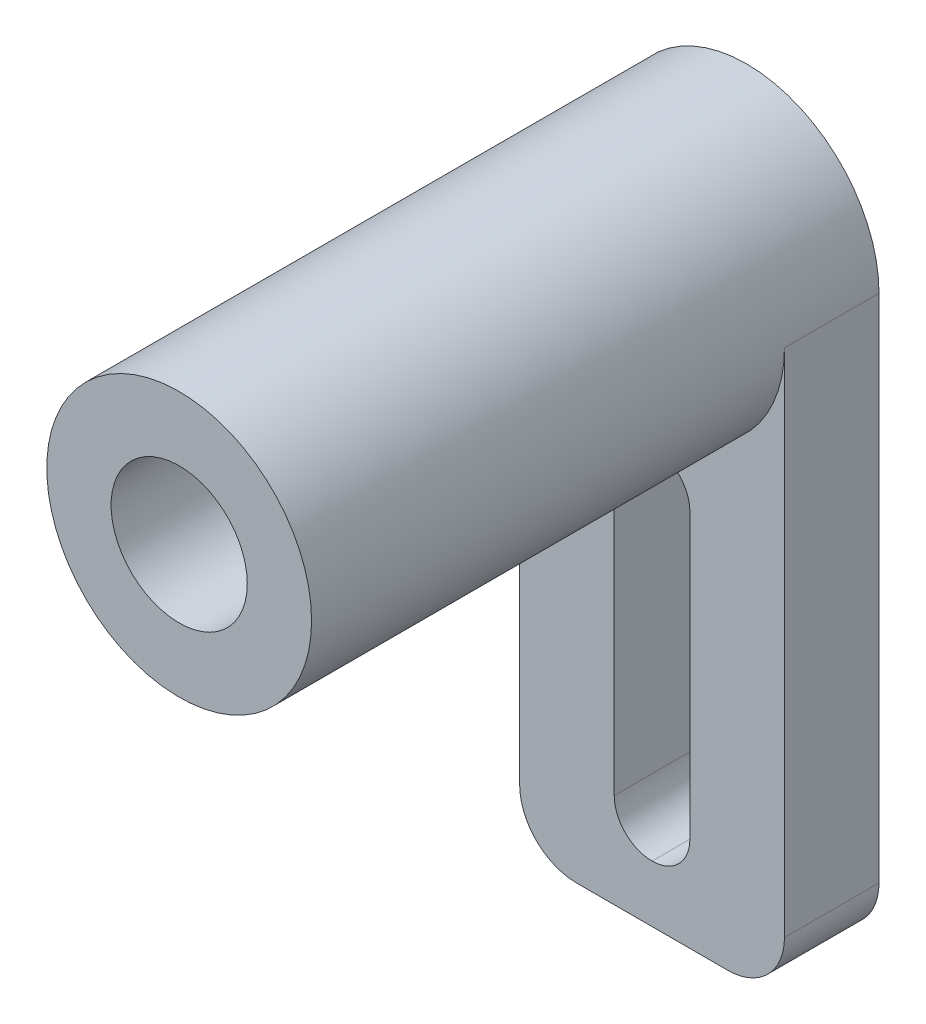
SolidWorks part; units mm, degrees
ref_plane "Płaszczyzna przednia" through (0, 0, 0) normal (0, 0, 1) x (1, 0, 0)
ref_plane "Płaszczyzna górna" through (0, 0, 0) normal (0, 1, 0) x (1, 0, 0)
ref_plane "Płaszczyzna prawa" through (0, 0, 0) normal (1, 0, 0) x (0, 0, -1)
sketch "Szkic1" plane through (0, 0, 0) normal (0, 0, 1) x (1, 0, 0)
  line L1 (0, 0) -> (14, 0)
  line L2 (0, 0) -> (0, 25)
  line L3 (0, 25) -> (14, 25)
  line L4 (14, 0) -> (14, 25)
extrude "Dodanie-wyciągnięcie1" add sketch "Szkic1" along normal blind 5
sketch "Szkic2" plane through (0, 0, 5) normal (0, 0, 1) x (1, 0, 0)
  line L1 (5, 22) -> (9, 22)
  line L2 (5, 22) -> (5, 3)
  line L3 (5, 3) -> (9, 3)
  line L4 (9, 22) -> (9, 3)
extrude "Wytnij-wyciągnięcie1" cut sketch "Szkic2" against normal blind 5
fillet "Zaokrąglenie1" radius 2 4 edges at (5, 3, 2.5) (9, 3, 2.5) (9, 22, 2.5) (5, 22, 2.5)
fillet "Zaokrąglenie2" radius 3 2 edges at (0, 0, 2.5) (14, 0, 2.5)
sketch "Szkic3" plane through (0, 0, 0) normal (0, 0, 1) x (1, 0, 0)
  circle A0 centre (7, 30) radius 3.05
  circle A1 centre (7, 30) radius 7
extrude "Dodanie-wyciągnięcie2" add sketch "Szkic3" along normal blind 30
sketch "Szkic4" plane through (0, 0, 0) normal (0, 0, -1) x (-1, 0, 0)
  line L0 (-14, 25) -> (-14, 30)
  line L1 (-14, 30) -> (-11.0048, 25)
  line L2 (-11.0048, 25) -> (-14, 25)
  line L3 (-2.101, 25) -> (0, 30)
  line L4 (0, 30) -> (0, 25)
  line L5 (0, 25) -> (-2.101, 25)
  arc A0 (-2.101, 25) -> (-11.899, 25) centre (-7, 30) ccw construction
extrude "Dodanie-wyciągnięcie3" add sketch "Szkic4" against normal blind 5
sketch "Szkic5" plane through (0, 0, 0) normal (0, 0, -1) x (-1, 0, 0)
  circle A0 centre (-7, 30) radius 5
  circle A1 centre (-7, 30) radius 2.2
extrude "Dodanie-wyciągnięcie4" add sketch "Szkic5" against normal blind 1
sketch "Szkic6" plane through (0, 0, 30) normal (0, 0, 1) x (1, 0, 0)
  circle A0 centre (7, 30) radius 3.6
extrude "Wytnij-wyciągnięcie2" cut sketch "Szkic6" against normal blind 22
sketch "Szkic8" [suppressed] plane through (0, 0, 30) normal (0, 0, 1) x (1, 0, 0)
  line L1 (16.5332, 28.6) -> (7, 28.6)
  line L2 (16.5332, 28.6) -> (16.5332, 31.4)
  line L3 (16.5332, 31.4) -> (7, 31.4)
  line L4 (7, 28.6) -> (7, 31.4)
extrude "Wytnij-wyciągnięcie3" [suppressed] cut sketch "Szkic8" against normal blind 6
fillet "Zaokrąglenie4" [suppressed] radius 1.4
